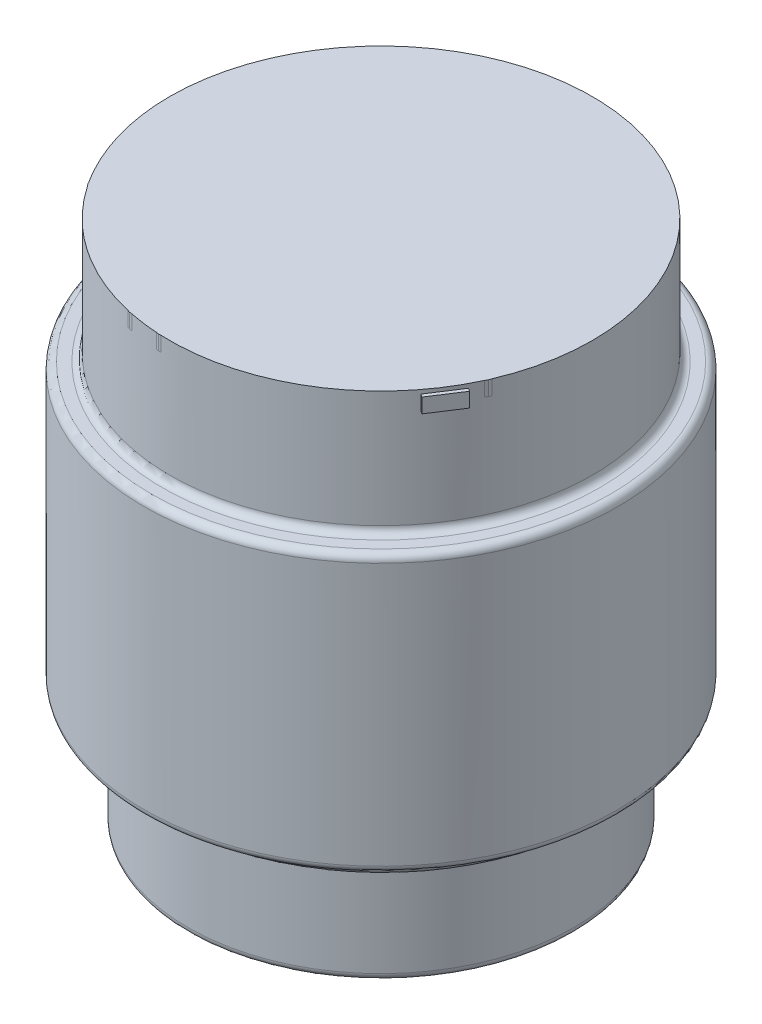
SolidWorks part; units mm, degrees
material "ABS"
ref_plane "Front Plane" through (0, 0, 0) normal (0, 0, 1) x (1, 0, 0)
ref_plane "Top Plane" through (0, 0, 0) normal (0, 1, 0) x (1, 0, 0)
ref_plane "Right Plane" through (0, 0, 0) normal (1, 0, 0) x (0, 0, -1)
sketch "Sketch1" plane through (0, 0, 0) normal (0, 0, 1) x (1, 0, 0)
  line L0 (0, 6.497) -> (0, -65.503) construction
  line L1 (0, 6.497) -> (29, 6.497) construction
  line L2 (0, 1.497) -> (29, 1.497) construction
  line L3 (0, -48.503) -> (32.5, -48.503) construction
  line L4 (0, -29.503) -> (32.5, -29.503) construction
  line L5 (0, 48.3985) -> (32.5, 48.3985) construction
  line L6 (0, -10.503) -> (47.5, -10.503) construction
  line L7 (0, -65.503) -> (26.5, -65.503) construction
  line L8 (0, -15.503) -> (32.5, -15.503) construction
  line L9 (0, -50.503) -> (30, -50.503) construction
  dimension "D1" = 72
  dimension "D2" = 29
  dimension "D4" = 32.5
  dimension "D5" = 32.5
  dimension "D7" = 19
  dimension "D8" = 19
  dimension "D6" = 5
  dimension "D9" = 12
  dimension "D10" = 17
  dimension "D11" = 5
  dimension "D12" = 32.5
  dimension "D13" = 47.5
  dimension "D14" = 15
  dimension "D15" = 26.5
  dimension "D3" = 30
  dimension "D16" = 32.5
  dimension "D17" = 29
sketch "Sketch10" plane through (0, 0, 0) normal (0, 0, 1) x (1, 0, 0)
  line L0 (0, 6.497) -> (29, 6.497)
  line L1 (29, 6.497) -> (29, -10.503)
  line L2 (0, -10.503) -> (47.5, -10.503) construction
  line L3 (29, -10.503) -> (32.5, -10.503)
  line L4 (32.5, -10.503) -> (32.5, -48.503)
  line L5 (32.5, -48.503) -> (30, -48.503)
  line L6 (0, -48.503) -> (32.5, -48.503) construction
  line L7 (30, -48.503) -> (30, -50.503)
  line L8 (30, -50.503) -> (26.5, -50.503)
  line L9 (0, -50.503) -> (30, -50.503) construction
  line L10 (26.5, -50.503) -> (26.5, -65.503)
  line L11 (26.5, -65.503) -> (0, -65.503)
revolve "Revolve-Thin6" add sketch "Sketch10" angle 360 about L0
sketch "Sketch11" plane through (0, 6.497, 0) normal (0, 1, 0) x (1, 0, 0)
  text T0 "nikkor AF 50mm F1_8" font "Arial Narrow" height in points 28
extrude "Boss-Extrude4" add sketch "Sketch11" against normal offset from surface (2 mm away) 2 up to face at (-29, 6.497, 0)
fillet "Fillet6" radius 1 1 edges at (-29, -10.503, 0)
fillet "Fillet7" radius 1 6 edges at (-26.5, -65.503, 0) (-26.5, -50.503, 0) (-30, -50.503, 0) (-30, -48.503, 0) (-32.5, -48.503, 0) (-32.5, -10.503, 0)
equation "\"D5@Sketch1\"=65/2"
equation "\"D4@Sketch1\"=65/2"
equation "\"D2@Sketch1\"=58/2"
equation "\"D12@Sketch1\"=65/2"
equation "\"D13@Sketch1\"=95/2"
equation "\"D15@Sketch1\"=53/2"
equation "\"D3@Sketch1\"=60/2"
equation "\"D16@Sketch1\"=65/2"
